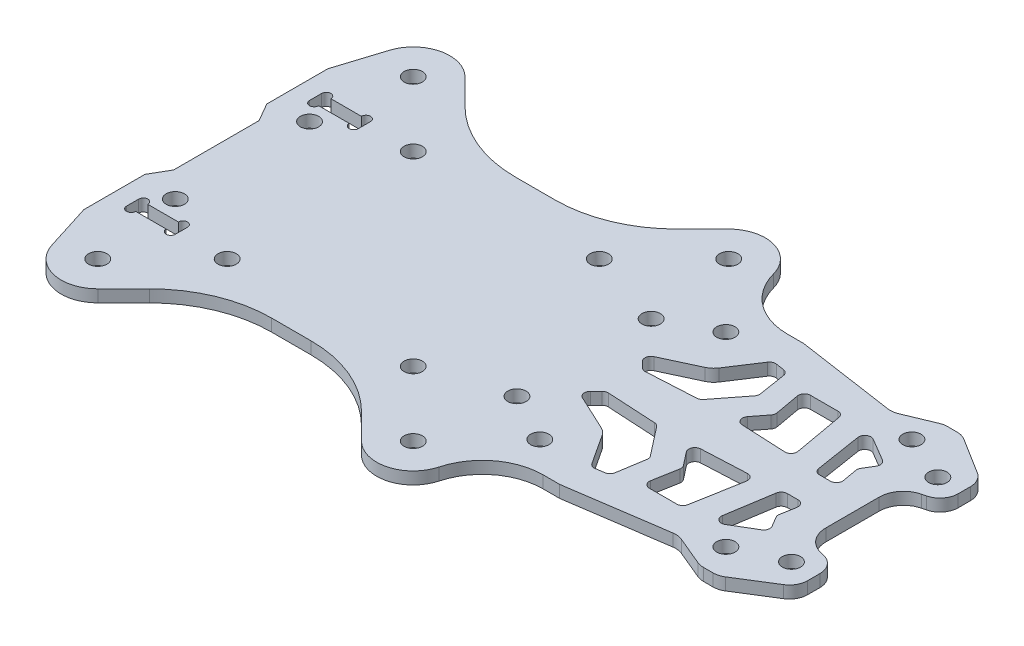
SolidWorks part; units mm, degrees
ref_plane "Front Plane" through (0, 0, 0) normal (0, 0, 1) x (1, 0, 0)
ref_plane "Top Plane" through (0, 0, 0) normal (0, 1, 0) x (1, 0, 0)
ref_plane "Right Plane" through (0, 0, 0) normal (1, 0, 0) x (0, 0, -1)
sketch "Sketch1" plane through (0, 0, 0) normal (0, 1, 0) x (1, 0, 0)
  line L0 (-34, 20) -> (78, 20)
  line L1 (-15.25, 15.25) -> (15.25, 15.25) construction
  line L2 (-15.25, 15.25) -> (-15.25, -15.25) construction
  line L3 (-15.25, -15.25) -> (15.25, -15.25) construction
  line L4 (15.25, 15.25) -> (15.25, -15.25) construction
  line L5 (-15.25, 15.25) -> (15.25, -15.25) construction
  line L6 (-15.25, -15.25) -> (15.25, 15.25) construction
  line L7 (-28, 17) -> (28, 17) construction
  line L8 (-28, -17) -> (-28, 17) construction
  line L9 (-28, -17) -> (28, -17) construction
  line L10 (28, 17) -> (28, -17) construction
  line L11 (-28, 17) -> (28, -17) construction
  line L12 (-28, -17) -> (28, 17) construction
  line L13 (78, 20) -> (78, -20)
  line L14 (78, -20) -> (-11.5147, -20)
  line L15 (-34, -20) -> (-34, 20)
  line L16 (28, 17) -> (74, 17) construction
  line L17 (74, 17) -> (74, -17) construction
  line L18 (74, -17) -> (28, -17) construction
  line L19 (44, -20) -> (78, -15)
  line L20 (44, 20) -> (78, 15)
  line L21 (-34, -14) -> (-23, -14) construction
  line L22 (-34, 14) -> (-23, 14) construction
  line L23 (-23, -14) -> (-23, -16)
  line L24 (-23, -16) -> (-31, -16)
  line L25 (-31, -16) -> (-31, -14)
  line L26 (-15.25, -15.25) -> (-38.7303, -38.7303) construction
  line L27 (-11.5147, -20) -> (-21.614, -30.0992)
  line L28 (-28.4853, -20) -> (-30.0992, -21.614)
  line L29 (-25.8566, -25.8566) -> (-30.0992, -21.614) construction
  line L30 (-28.4853, -20) -> (-34, -20)
  line L31 (-15.25, 0) -> (15.25, 0) construction
  line L32 (0, -15.25) -> (0, 15.25) construction
  line L33 (-15.25, 15.25) -> (-38.7303, 38.7303) construction
  line L34 (-28.4853, 20) -> (-30.0992, 21.614)
  line L35 (-11.5147, 20) -> (-21.614, 30.0992)
  line L36 (-25.8566, 25.8566) -> (-30.0992, 21.614) construction
  line L37 (25.8566, -25.8566) -> (30.0992, -21.614) construction
  line L38 (25.8566, 25.8566) -> (30.0992, 21.614) construction
  line L39 (28.4853, -20) -> (30.0992, -21.614)
  line L40 (11.5147, -20) -> (21.614, -30.0992)
  line L41 (15.25, -15.25) -> (38.7303, -38.7303) construction
  line L42 (15.25, 15.25) -> (38.7303, 38.7303) construction
  line L43 (28.4853, 20) -> (30.0992, 21.614)
  line L44 (11.5147, 20) -> (21.614, 30.0992)
  line L45 (78, -9) -> (72, -7.5)
  line L46 (72, -7.5) -> (72, 7.5)
  line L47 (72, 7.5) -> (78, 9)
  line L48 (-23, 14) -> (-23, 16)
  line L49 (-23, 16) -> (-31, 16)
  line L50 (-31, 16) -> (-31, 14)
  line L51 (-31, -14) -> (-23, -14)
  line L52 (-31, 14) -> (-23, 14)
  line L53 (-32.2742, -7) -> (-34.0042, -10)
  line L54 (-32.2742, 6.998) -> (-34.0042, 10)
  line L55 (-32.2742, -7) -> (-32.2742, 6.998)
  line L56 (61, -17.5) -> (67, -20)
  line L57 (67, -20) -> (75, -20)
  line L58 (61, 17.5) -> (67, 20)
  line L59 (67, 20) -> (75, 20)
  line L60 (78, -15) -> (70, -20)
  line L61 (78, 15) -> (70, 20)
  line L62 (-34, -20) -> (-34, -21.3726)
  circle A0 centre (28, -11) radius 1.5
  circle A1 centre (28, 11) radius 1.5
  circle A2 centre (15.25, 15.25) radius 1.5
  circle A3 centre (-15.25, 15.25) radius 1.5
  circle A4 centre (-15.25, -15.25) radius 1.5
  circle A5 centre (15.25, -15.25) radius 1.5
  arc A6 (-31, -16) -> (-29.5, -16) centre (-30.25, -16) ccw
  arc A7 (-23, -16) -> (-24.5, -16) centre (-23.75, -16) cw
  circle A8 centre (74, -12) radius 1.5
  circle A9 centre (74, 12) radius 1.5
  circle A10 centre (-25.8566, -25.8566) radius 1.5
  arc A11 (-30.0992, -21.614) -> (-21.614, -30.0992) centre (-25.8566, -25.8566) ccw
  arc A12 (-30.0992, 21.614) -> (-21.614, 30.0992) centre (-25.8566, 25.8566) cw
  circle A13 centre (-25.8566, 25.8566) radius 1.5
  circle A14 centre (25.8566, -25.8566) radius 1.5
  arc A15 (30.0992, -21.614) -> (21.614, -30.0992) centre (25.8566, -25.8566) cw
  circle A16 centre (25.8566, 25.8566) radius 1.5
  arc A17 (30.0992, 21.614) -> (21.614, 30.0992) centre (25.8566, 25.8566) ccw
  arc A18 (-23, -14) -> (-24.5, -14) centre (-23.75, -14) ccw
  arc A19 (-31, -14) -> (-29.5, -14) centre (-30.25, -14) cw
  arc A20 (-31, 14) -> (-29.5, 14) centre (-30.25, 14) ccw
  arc A21 (-31, 16) -> (-29.5, 16) centre (-30.25, 16) cw
  arc A22 (-23, 16) -> (-24.5, 16) centre (-23.75, 16) ccw
  arc A23 (-23, 14) -> (-24.5, 14) centre (-23.75, 14) cw
  circle A24 centre (-28, -11) radius 1.5
  circle A25 centre (-28, 11) radius 1.5
  point P0 (0, 0)
  point P6 (0, 0)
  dimension "D11" = 3
  dimension "D12" = 3
  dimension "D9" = 6
  dimension "D10" = 8
  dimension "D19" = 3
  dimension "D20" = 3
  dimension "D21" = 3
  dimension "D22" = 3
  dimension "D23" = 3
  dimension "D24" = 3
  dimension "D33" = 3
  dimension "D26" = 2
  dimension "D45" = 3
  dimension "D46" = 3
  dimension "D1" = 30.5
  dimension "D2" = 30.5
  dimension "D3" = 56
  dimension "D4" = 34
  dimension "D5" = 40
  dimension "D6" = 3
  dimension "D7" = 50
  dimension "D8" = 28
  dimension "D13" = 8
  dimension "D14" = 8
  dimension "D15" = 34
  dimension "D16" = 34
  dimension "D17" = 5
  dimension "D18" = 5
  dimension "D25" = 4
  dimension "D27" = 3
  dimension "D28" = 8
  dimension "D29" = 3
  dimension "D30" = 45
  dimension "D31" = 6
  dimension "D32" = 6
  dimension "D34" = 15
  dimension "D35" = 6
  dimension "D36" = 6
  dimension "D37" = 1.5
  dimension "D38" = 1.5
  dimension "D39" = 6
  dimension "D40" = 2
  dimension "D41" = 1.5
  dimension "D42" = 1.5
  dimension "D43" = 1.5
  dimension "D44" = 1.5
  dimension "D47" = 3
  dimension "D48" = 3
  dimension "D49" = 9
  dimension "D50" = 9
  dimension "D51" = 1
  dimension "D52" = 1
  dimension "D53" = 3.002
  dimension "D54" = 3
  dimension "D55" = 8
  dimension "D56" = 8
  dimension "D57" = 3
  dimension "D58" = 8
  dimension "D59" = 6
  dimension "D60" = 6
  dimension "D61" = 8
extrude "Boss-Extrude1" add sketch "Sketch1" along normal blind 2 contours A12 L34 L0 L35 A13 | L43 A17 L44 L0 A16 | A15 L39 L14 L40 A14 | L0 L15 | L60 L19 L56 L57 | L20 L61 L0 L58 region at (18.3063, 0, 0.8792) region at (-23.5596, 0, -24.9275) region at (23.5596, 0, -24.9275) region at (69.2874, 0, -17.6724) region at (23.5596, 0, 24.9275) region at (69.2874, 0, 17.6724)
fillet "Fillet1" radius 20 4 edges at (11.5147, 1, -20) (-11.5147, 1, -20) (11.5147, 1, 20) (-11.5147, 1, 20)
fillet "Fillet2" radius 10 2 edges at (28.4853, 1, -20) (28.4853, 1, 20)
fillet "Fillet8" radius 10000 2 edges at (-28.4853, 1, -20) (-28.4853, 1, 20)
fillet "Fillet9" radius 3 10 edges at (78, 1, -9) (78, 1, 9) (67, 1, -20) (61, 1, -17.5) (61, 1, 17.5) (67, 1, 20) (70, 1, -20) (78, 1, -15) (70, 1, 20) (78, 1, 15)
fillet "Fillet10" radius 4 2 edges at (72, 1, 7.5) (72, 1, -7.5)
sketch "Sketch2" plane through (0, 2, 0) normal (0, 1, 0) x (1, 0, 0)
  line L0 (15.25, -15.25) -> (74, -15.25) construction
  line L1 (74, 17) -> (74, -17) construction
  line L2 (15.25, 15.25) -> (74, 15.25) construction
  line L3 (28, 17) -> (28, -17) construction
  circle A0 centre (36, -15.25) radius 1.5
  circle A1 centre (36, 15.25) radius 1.5
  circle A2 centre (66.5, -15.25) radius 1.5
  circle A3 centre (66.5, 15.25) radius 1.5
  dimension "D1" = 3
  dimension "D2" = 3
  dimension "D5" = 3
  dimension "D6" = 3
  dimension "D3" = 8
  dimension "D4" = 8
  dimension "D7" = 30.5
  dimension "D8" = 30.5
extrude "Cut-Extrude1" cut sketch "Sketch2" against normal through all contours A2 | A3 | A0 | A1 region at (36, 2, 15.25) region at (36, 2, -15.25) region at (66.5, 2, 15.25) region at (66.5, 2, -15.25)
sketch "Sketch3" plane through (0, 2, 0) normal (0, 1, 0) x (1, 0, 0)
  line L0 (72, 0) -> (16.9083, 0) construction
  line L1 (72, -4.3769) -> (72, 4.3769) construction
  line L2 (32.3114, -5.2577) -> (34.5691, -3)
  line L3 (34.5691, -3) -> (43.4782, -3.4972)
  line L4 (43.4782, -3.4972) -> (47.6826, -8.8848)
  line L5 (47.6826, -8.8848) -> (46.7744, -14.5382)
  line L6 (44.0463, -14.9394) -> (46.7744, -14.5382)
  line L7 (44.0463, -14.9394) -> (40.0838, -8.8848)
  line L8 (40.0838, -8.8848) -> (32.3114, -5.2577)
  line L9 (48.5936, -3.4972) -> (51.7469, -7.5264)
  line L10 (51.7469, -7.5264) -> (50.7308, -13.2023)
  line L11 (50.7308, -13.2023) -> (57.2476, -13.2023)
  line L12 (57.2476, -13.2023) -> (59.074, -3)
  line L13 (59.074, -3) -> (48.5936, -3.4972)
  line L14 (61.4463, -13.2023) -> (67.8693, -9.3969)
  line L15 (44, -20) -> (60.1773, -17.621) construction
  line L16 (67.8693, -9.3969) -> (66.2198, -6.6128)
  line L17 (66.2198, -6.6128) -> (66.93, -2.6454)
  line L18 (66.93, -2.6454) -> (63.1149, -2.6454)
  line L19 (63.1149, -2.6454) -> (61.4463, -13.2023)
  line L20 (61.4463, -13.2023) -> (61.2257, -13.188)
  line L21 (61.4463, 13.2023) -> (61.2257, 13.188)
  line L22 (40.0838, 8.8848) -> (32.3114, 5.2577)
  line L23 (44.0463, 14.9394) -> (40.0838, 8.8848)
  line L24 (44.0463, 14.9394) -> (46.7744, 14.5382)
  line L25 (47.6826, 8.8848) -> (46.7744, 14.5382)
  line L26 (43.4782, 3.4972) -> (47.6826, 8.8848)
  line L27 (34.5691, 3) -> (43.4782, 3.4972)
  line L28 (32.3114, 5.2577) -> (34.5691, 3)
  line L29 (63.1149, 2.6454) -> (61.4463, 13.2023)
  line L30 (66.93, 2.6454) -> (63.1149, 2.6454)
  line L31 (66.2198, 6.6128) -> (66.93, 2.6454)
  line L32 (67.8693, 9.3969) -> (66.2198, 6.6128)
  line L33 (61.4463, 13.2023) -> (67.8693, 9.3969)
  line L34 (59.074, 3) -> (48.5936, 3.4972)
  line L35 (57.2476, 13.2023) -> (59.074, 3)
  line L36 (50.7308, 13.2023) -> (57.2476, 13.2023)
  line L37 (51.7469, 7.5264) -> (50.7308, 13.2023)
  line L38 (48.5936, 3.4972) -> (51.7469, 7.5264)
  dimension "D1" = 5
  dimension "D2" = 3
extrude "Cut-Extrude2" cut sketch "Sketch3" against normal through all contours L22 L28 L27 L26 L25 L24 L23 | L8 L7 L6 L5 L4 L3 L2 | L17 L16 | L12 L13 L9 L10 L11 | L38 L34 L35 L36 L37 | L33 L29 L30 L31 L32 region at (41.6046, 2, 7.8128) region at (54.4665, 2, 7.8017) region at (64.4318, 2, 7.5009) region at (41.6046, 2, -7.8128) region at (64.4318, 2, -7.5009) region at (54.4665, 2, -7.8017)
fillet "Fillet11" radius 1 32 edges at (66.2198, 1, 6.6128) (46.7744, 1, -14.5382) (44.0463, 1, -14.9394) (47.6826, 1, -8.8848) (43.4782, 1, -3.4972) (34.5691, 1, -3) (32.3114, 1, -5.2577) (44.0463, 1, 14.9394) (46.7744, 1, 14.5382) (47.6826, 1, 8.8848) (43.4782, 1, 3.4972) (34.5691, 1, 3) (32.3114, 1, 5.2577) (51.7469, 1, 7.5264) (51.7469, 1, -7.5264) (67.8693, 1, -9.3969) (61.4463, 1, -13.2023) (66.93, 1, -2.6454) (66.2198, 1, -6.6128) (66.93, 1, 2.6454) (67.8693, 1, 9.3969) (61.4463, 1, 13.2023) (63.1149, 1, 2.6454) (63.1149, 1, -2.6454) (59.074, 1, -3) (57.2476, 1, -13.2023) (50.7308, 1, -13.2023) (48.5936, 1, -3.4972) (50.7308, 1, 13.2023) (57.2476, 1, 13.2023) (59.074, 1, 3) (48.5936, 1, 3.4972)
fillet "Fillet12" radius 3 2 edges at (40.0838, 1, -8.8848) (40.0838, 1, 8.8848)
